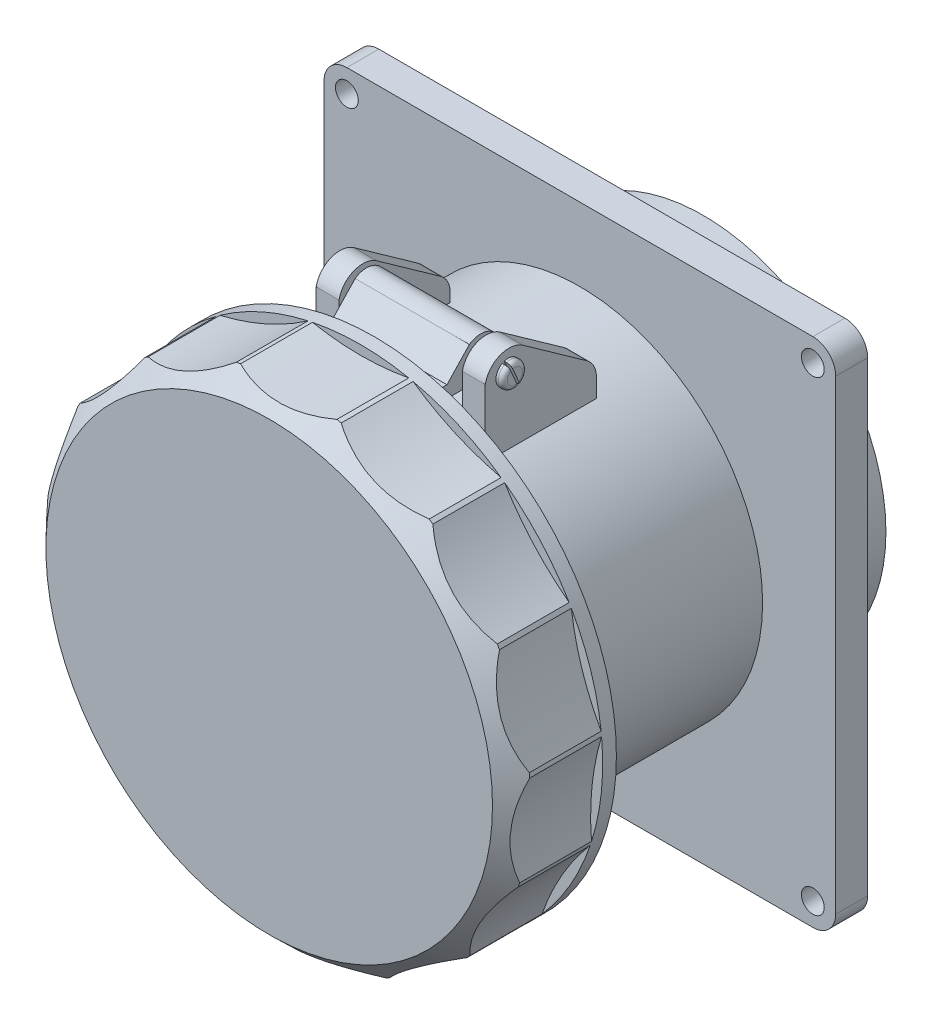
SolidWorks part; units mm, degrees
ref_plane "Plano frontal" through (0, 0, 0) normal (0, 0, 1) x (1, 0, 0)
ref_plane "Plano superior" through (0, 0, 0) normal (0, 1, 0) x (1, 0, 0)
ref_plane "Plano direito" through (0, 0, 0) normal (1, 0, 0) x (0, 0, -1)
sketch "Esboço1" plane through (0, 0, 0) normal (0, 0, 1) x (1, 0, 0)
  line L1 (-51, 56) -> (51, 56)
  line L2 (-56, 51) -> (-56, -51)
  line L3 (-51, -56) -> (51, -56)
  line L4 (56, 51) -> (56, -51)
  arc A0 (-51, 56) -> (-56, 51) centre (-51, 51) ccw
  arc A1 (51, 56) -> (56, 51) centre (51, 51) cw
  arc A2 (51, -56) -> (56, -51) centre (51, -51) ccw
  arc A3 (-56, -51) -> (-51, -56) centre (-51, -51) ccw
  circle A4 centre (-51, 51) radius 2.5
  circle A5 centre (51, 51) radius 2.5
  circle A6 centre (51, -51) radius 2.5
  circle A7 centre (-51, -51) radius 2.5
  point P9 (56, 56)
  point P12 (56, -56)
  point P15 (-56, -56)
  dimension "D5" = 5
  dimension "D6" = 5
  dimension "D1" = 112
  dimension "D2" = 56
  dimension "D3" = 112
  dimension "D4" = 56
  dimension "D7" = 5
  dimension "D8" = 5
extrude "Extrusão1" add sketch "Esboço1" along normal blind 7
sketch "Esboço2" plane through (0, 0, 7) normal (0, 0, 1) x (1, 0, 0)
  arc A0 (7.467, -39.2969) -> (-7.467, -39.2969) centre (0, 0) ccw
  arc A1 (-7.467, -39.2969) -> (7.467, -39.2969) centre (0, -40) ccw
  dimension "D1" = 80
extrude "Extrusão2" add sketch "Esboço2" along normal blind 45
sketch "Esboço3" plane through (0, 0, 52) normal (0, 0, 1) x (1, 0, 0)
  circle A0 centre (0, 0) radius 53
  dimension "D1" = 106
extrude "Extrusão3" add sketch "Esboço3" along normal blind 23
sketch "Esboço4" plane through (0, 0, 75) normal (0, 0, 1) x (1, 0, 0)
  line L0 (-10.5423, 51.9409) -> (-10.5423, 54.2056)
  line L1 (-10.5423, 54.2056) -> (10.5423, 54.2056)
  line L2 (10.5423, 54.2056) -> (10.5423, 51.9409)
  arc A0 (10.5423, 51.9409) -> (-10.5423, 51.9409) centre (0, 107.0856) cw
  circle A1 centre (0, 0) radius 53 construction
extrude "Corte-extrusão1" cut sketch "Esboço4" against normal blind 20
pattern_circular "CirPattern1" count 15 over 360 about axis through (0, 0, 52) along (0, 0, -1) of "Corte-extrusão1"
sketch "Esboço5" plane through (56, 0, 0) normal (1, 0, 0) x (0, 0, -1)
  line L0 (-52, 48.4252) -> (-48.5901, 48.4252)
  line L1 (-52, -53) -> (-52, 53) construction
  line L2 (-52, 45.7774) -> (-41.2084, 45.7774)
  line L3 (-43.6813, 53.6011) -> (-48.5901, 48.4252)
  line L4 (-52, 48.4252) -> (-53.584, 48.4252)
  line L5 (-53.584, 48.4252) -> (-53.584, 45.7774)
  line L6 (-53.584, 45.7774) -> (-52, 45.7774)
  arc A0 (-41.2084, 45.7774) -> (-43.6813, 53.6011) centre (-41.2084, 50.08) ccw
  circle A1 centre (-41.2084, 50.08) radius 2
  dimension "D1" = 4
extrude "Extrusão4" add sketch "Esboço5" against normal blind 25 from offset 43.5 offset against normal yes
sketch "Esboço6" plane through (12.5, 0, 0) normal (1, 0, 0) x (0, 0, -1)
  line L0 (-46.2097, 50.2765) -> (-46.2097, 26.1652)
  line L1 (-46.2097, 26.1652) -> (-21.8763, 26.1652)
  line L2 (-21.8763, 26.1652) -> (-21.8763, 39.5941)
  line L3 (-23.9812, 43.6707) -> (-37.9568, 53.5961)
  arc A0 (-37.9568, 53.5961) -> (-46.2097, 50.2765) centre (-41.0174, 49.2864) ccw
  arc A1 (-21.8763, 39.5941) -> (-23.9812, 43.6707) centre (-26.8763, 39.5941) ccw
  dimension "D1" = 5
extrude "Extrusão5" add sketch "Esboço6" along normal blind 5 from offset 1
mirror "Espelhar1" about plane through (0, 0, 0) normal (1, 0, 0) of "Extrusão5"
sketch "Esboço7" plane through (18.5, 0, 0) normal (1, 0, 0) x (0, 0, -1)
  line L0 (-42.4855, 52.4144) -> (-40.3907, 47.548)
  line L2 (-39.9621, 47.7291) -> (-42.0593, 52.6012)
  arc A0 (-42.4855, 52.4144) -> (-40.3907, 47.548) centre (-41.2084, 50.08) ccw
  arc A1 (-39.9621, 47.7291) -> (-42.0593, 52.6012) centre (-41.2084, 50.08) ccw
extrude "Extrusão6" add sketch "Esboço7" along normal blind 1.5
fillet "Filete1" radius 1 2 edges at (20, 51.1321, 38.7644) (20, 49.028, 43.6525)
mirror "Espelhar2" about plane through (0, 0, 0) normal (1, 0, 0) of "Extrusão6", "Filete1"
sketch "Esboço8" plane through (0, 0, 0) normal (0, 0, -1) x (-1, 0, 0)
  circle A0 centre (0, 0) radius 40
extrude "Extrusão7" add sketch "Esboço8" along normal blind 20
sketch "Esboço9" plane through (0, 0, 75) normal (0, 0, 1) x (1, 0, 0)
  circle A0 centre (0, 0) radius 48.8768
extrude "Corte-extrusão2" cut sketch "Esboço9" against normal blind 10 draft 44 flip side to cut
